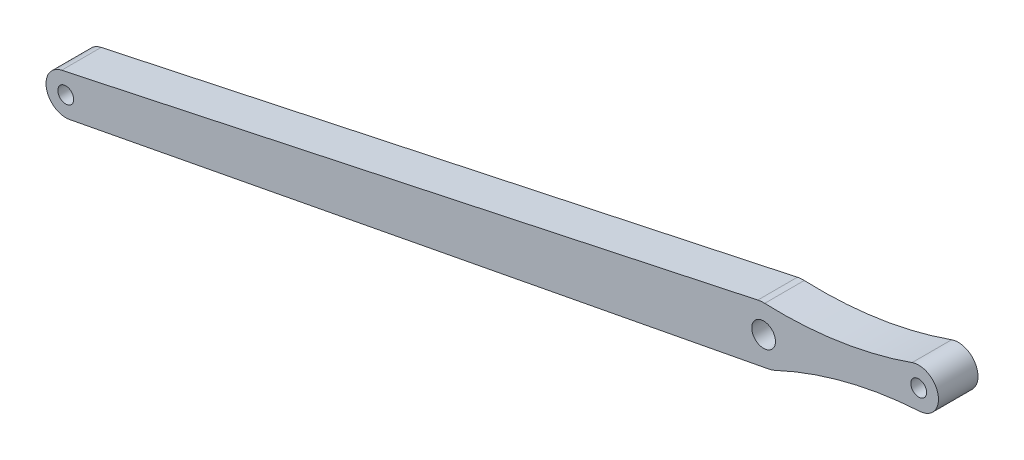
SolidWorks part; units mm, degrees
ref_plane "Front Plane" through (0, 0, 0) normal (0, 0, 1) x (1, 0, 0)
ref_plane "Top Plane" through (0, 0, 0) normal (0, 1, 0) x (1, 0, 0)
ref_plane "Right Plane" through (0, 0, 0) normal (1, 0, 0) x (0, 0, -1)
sketch "Sketch1" plane through (0, 0, 0) normal (0, 0, 1) x (1, 0, 0)
  line L0 (-61.8532, 154.8443) -> (-237.8537, 117.1637)
  line L3 (-59.0748, 141.1237) -> (-235.8691, 107.3632)
  circle A2 centre (-60.3878, 147.9994) radius 7
  circle A3 centre (-236.8069, 112.2745) radius 5
  circle A4 centre (-21.1835, 155.9383) radius 5
  arc A5 (-60.1155, 154.9941) -> (-22.8522, 160.6516) centre (-56.2254, 254.9184) ccw
  arc A6 (-20.887, 150.9471) -> (-57.4156, 141.6617) centre (-14.9568, 51.1231) ccw
  circle A7 centre (-236.8069, 112.2745) radius 2 construction
  circle A8 centre (-236.8069, 112.2745) radius 2
  circle A9 centre (-60.3878, 147.9994) radius 3 construction
  circle A10 centre (-60.3878, 147.9994) radius 3
  circle A11 centre (-21.1835, 155.9383) radius 2 construction
  circle A12 centre (-21.1835, 155.9383) radius 2
  dimension "D1" = 14
  dimension "D2" = 10
  dimension "D3" = 10
  dimension "D4" = 100
  dimension "D5" = 100
extrude "Boss-Extrude1" add sketch "Sketch1" along normal blind 5 and the other way blind 5 contours A3 L3 A2 L0 | A3 | A2 | A6 A4 A5 A2 | A4 region at (-144.9754, 130.8704, 0) region at (-60.972, 154.7763, 0) region at (-233.7521, 116.0526, 0) region at (-40.6388, 151.9986, 0) region at (-18.3792, 159.9059, 0)
